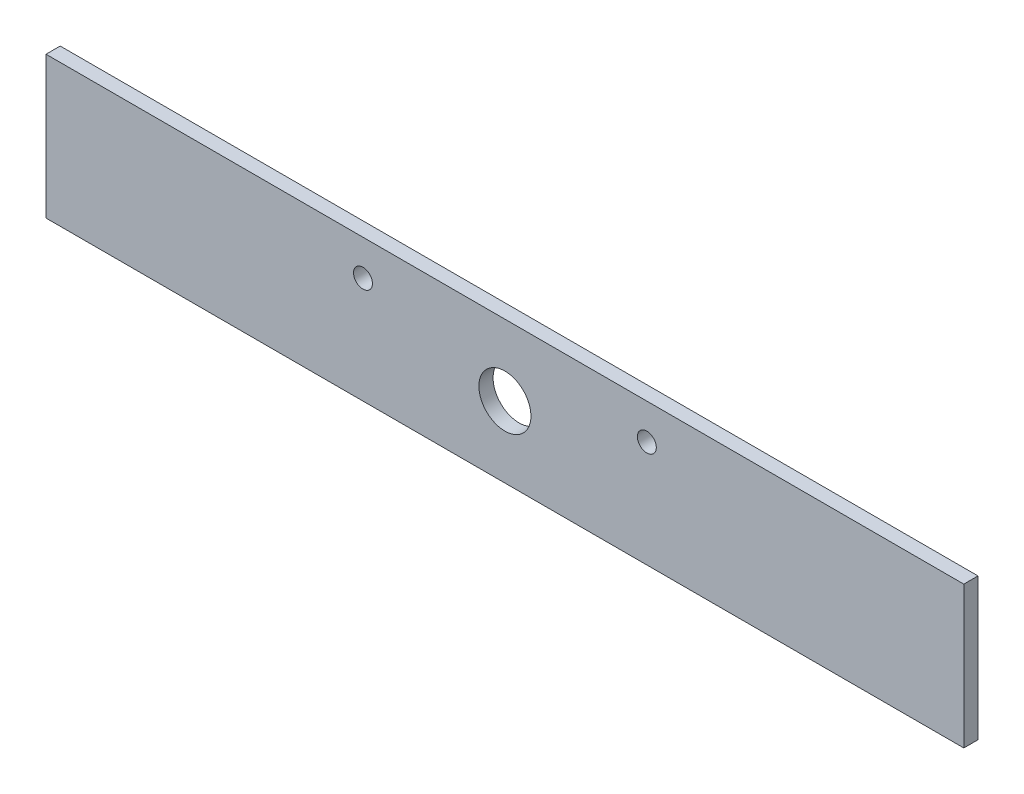
SolidWorks part; units mm, degrees
ref_plane "Front Plane" through (0, 0, 0) normal (0, 0, 1) x (1, 0, 0)
ref_plane "Top Plane" through (0, 0, 0) normal (0, 1, 0) x (1, 0, 0)
ref_plane "Right Plane" through (0, 0, 0) normal (1, 0, 0) x (0, 0, -1)
sketch "Sketch1" plane through (0, 0, 0) normal (0, 0, 1) x (1, 0, 0)
  line L0 (0, -1000) -> (0, 49000) construction
  line L1 (-194, -30) -> (194, -30)
  line L3 (-194, 30) -> (194, 30)
  line L7 (-1000, 0) -> (49000, 0) construction
  line L8 (194, 30) -> (194, -30)
  line L20 (-194, 30) -> (-194, -30)
  line L25 (-1000, 15) -> (49000, 15) construction
  circle A4 centre (60, 15) radius 4
  circle A5 centre (-60, 15) radius 4
  circle A14 centre (0, 0) radius 11
  point P0 (0, 0)
  point P24 (0, -30)
  dimension "D10" = 60
  dimension "D4" = 8
  dimension "D13" = 388
  dimension "D14" = 60
  dimension "D2" = 22
  dimension "D5" = 60
  dimension "D3" = 15
  dimension "D16" = 15
extrude "Boss-Extrude1" add sketch "Sketch1" along normal blind 6 contours L1 L8 L3 L20 A5 region at (-190.0739, 0, 0)
